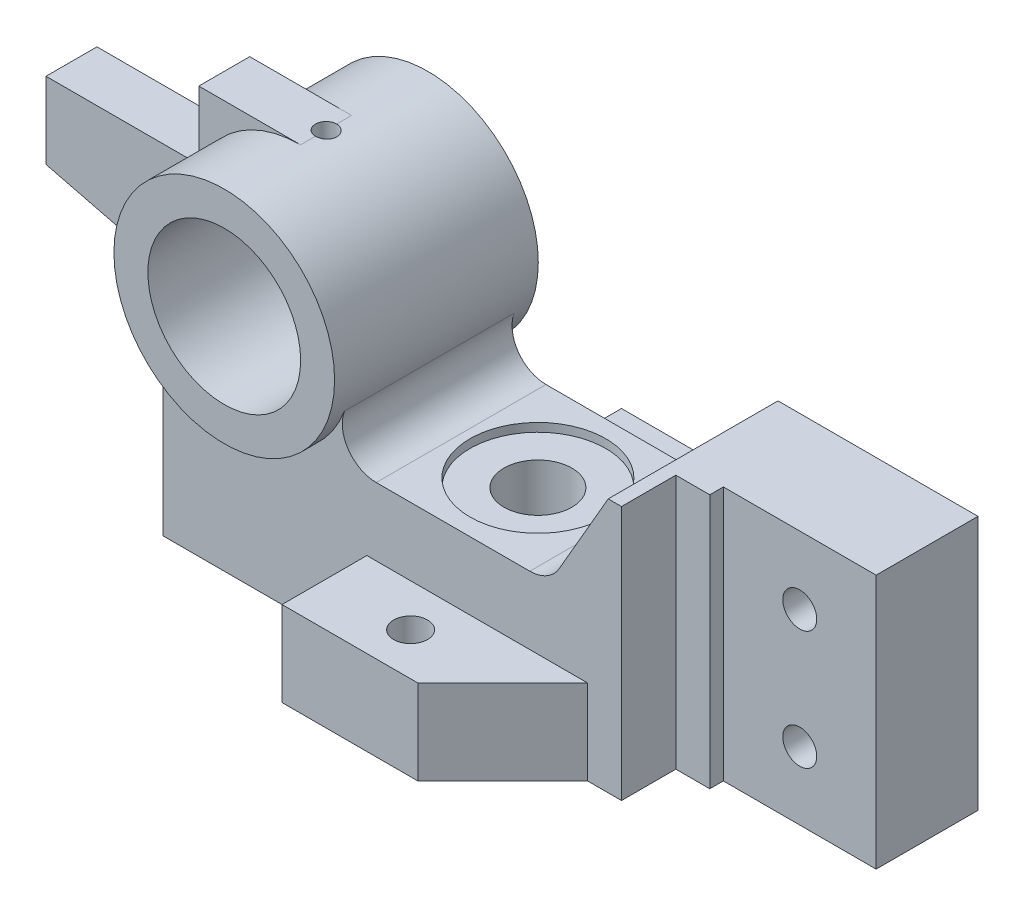
SolidWorks part; units mm, degrees
ref_plane "Front Plane" through (0, 0, 0) normal (0, 0, 1) x (1, 0, 0)
ref_plane "Top Plane" through (0, 0, 0) normal (0, 1, 0) x (1, 0, 0)
ref_plane "Right Plane" through (0, 0, 0) normal (1, 0, 0) x (0, 0, -1)
sketch "Sketch1" plane through (0, 0, 0) normal (0, 0, 1) x (1, 0, 0)
  line L0 (0, 20.6375) -> (-19.05, 20.6375)
  line L1 (-19.05, 20.6375) -> (-19.05, 7.9375)
  line L2 (-19.05, 7.9375) -> (-47.625, 7.9375)
  line L3 (-47.625, 7.9375) -> (-47.625, -6.35)
  line L4 (-47.625, -6.35) -> (-14.6024, -14.5835)
  line L5 (-14.6024, -14.5835) -> (-47.625, -14.5835) construction
  line L6 (-14.6024, -14.5835) -> (-14.6024, -44.45)
  line L7 (-14.6024, -44.45) -> (106.0476, -44.45)
  line L8 (25.2507, -15.875) -> (53.975, -15.875)
  line L9 (59.4743, -12.7) -> (68.6397, 3.175)
  line L10 (68.6397, 3.175) -> (68.6397, -44.45) construction
  line L11 (68.6397, 3.175) -> (106.0476, 3.175)
  line L12 (106.0476, 3.175) -> (106.0476, -44.45)
  line L13 (23.4976, -44.45) -> (23.4976, -28.575)
  line L14 (23.4976, -28.575) -> (64.7726, -28.575)
  line L15 (64.7726, -28.575) -> (64.7726, -44.45)
  circle A0 centre (0, 0) radius 14.2875
  circle A1 centre (0, 0) radius 20.6375
  arc A2 (19.3094, -7.2838) -> (25.2507, -15.875) centre (25.2507, -9.525) ccw
  arc A3 (53.975, -15.875) -> (59.4743, -12.7) centre (53.975, -9.525) ccw
  dimension "D1" = 41.275
  dimension "D2" = 28.575
  dimension "D3" = 12.7
  dimension "D13" = 6.35
  dimension "D4" = 12.7
  dimension "D5" = 14.2875
  dimension "D6" = 28.575
  dimension "D7" = 14
  dimension "D8" = 44.45
  dimension "D9" = 28.575
  dimension "D10" = 120.65
  dimension "D11" = 30
  dimension "D12" = 47.625
  dimension "D14" = 53.975
  dimension "D15" = 41.275
  dimension "D16" = 38.1
  dimension "D17" = 15.875
extrude "Boss-Extrude1" add sketch "Sketch1" along normal mid plane 9.525 contours A3 L8 A2 A1 L6 L7 L13 L14 L15 L12 L11 L9 | A1 A0 | A1 L2 L3 L4 | L15 L14 L13 L7 | A1 L0 L1 region at (-14.6264, 17.1702, 0) region at (14.1802, 14.1802, 0) region at (-32.5158, -1.367, 0) region at (55.8173, -23.7707, 0) region at (44.1351, -36.5125, 0)
extrude "Boss-Extrude2" add sketch "Sketch1<5>" along normal mid plane 38.1 contours A1 A0 region at (14.1802, 14.1802, 0)
sketch "Sketch1<5>" plane through (0, 0, 0) normal (0, 0, 1) x (1, 0, 0) same geometry as "Sketch1"
extrude "Boss-Extrude3" add sketch "Sketch1<6>" along normal mid plane 31.75 contours A3 L8 A2 A1 L6 L7 L13 L14 L15 L12 L11 L9 | L15 L14 L13 L7 region at (55.8173, -23.7707, 0) region at (44.1351, -36.5125, 0)
sketch "Sketch1<6>" plane through (0, 0, 0) normal (0, 0, 1) x (1, 0, 0) same geometry as "Sketch1"
extrude "Boss-Extrude4" add sketch "Sketch1<7>" along normal mid plane 63.5 contours L15 L14 L13 L7 region at (44.1351, -36.5125, 0)
sketch "Sketch1<7>" plane through (0, 0, 0) normal (0, 0, 1) x (1, 0, 0) same geometry as "Sketch1"
sketch "Sketch2" plane through (0, -15.875, 0) normal (0, 1, 0) x (1, 0, 0)
  line L0 (48.8976, -31.75) -> (64.7726, -15.875)
  line L1 (23.4976, -31.75) -> (64.7726, -31.75) construction
  line L2 (64.7726, -31.75) -> (64.7726, -15.875) construction
  line L3 (64.7726, -15.875) -> (64.7726, -31.75)
  line L4 (64.7726, -31.75) -> (48.8976, -31.75)
  line L5 (68.6397, -15.875) -> (106.0476, -15.875) construction
  line L6 (39.6129, 0) -> (106.0476, 0) construction
  line L7 (106.0476, -15.875) -> (106.0476, 15.875) construction
  line L8 (64.7726, 31.75) -> (48.8976, 31.75)
  line L9 (64.7726, 15.875) -> (64.7726, 31.75)
  line L10 (48.8976, 31.75) -> (64.7726, 15.875)
  line L12 (106.0476, -3.175) -> (77.4726, -3.175)
  line L13 (77.4726, -3.175) -> (77.4726, -5.715)
  line L14 (77.4726, -5.715) -> (71.1226, -5.715)
  line L15 (71.1226, -5.715) -> (71.1226, -15.875)
  line L16 (71.1226, -15.875) -> (106.0476, -15.875)
  line L17 (106.0476, -15.875) -> (106.0476, -3.175)
  line L18 (25.2507, -15.875) -> (53.975, -15.875) construction
  circle A0 centre (39.6129, 0) radius 12.7
  circle A1 centre (39.6129, 0) radius 6.35
  point P21 (39.6129, -15.875)
  dimension "D1" = 25.4
  dimension "D2" = 12.7
  dimension "D3" = 15.875
  dimension "D5" = 28.575
  dimension "D6" = 6.35
  dimension "D7" = 12.7
  dimension "D8" = 2.54
extrude "Cut-Extrude1" cut sketch "Sketch2" against normal through all and the other way through all contours A1 | L4 L3 L0 | L8 L10 L9 | L16 L17 L12 L13 L14 L15 region at (59.481, -15.875, 26.4583) region at (59.481, -15.875, -26.4583) region at (89.1243, -15.875, 9.7167) region at (39.6129, -15.875, 0)
extrude "Cut-Extrude4" cut sketch "Sketch2<5>" against normal blind 1.5875
sketch "Sketch2<5>" plane through (0, -15.875, 0) normal (0, 1, 0) x (1, 0, 0) same geometry as "Sketch2"
sketch "Sketch3" plane through (0, -28.575, 0) normal (0, 1, 0) x (1, 0, 0)
  line L0 (39.6129, -23.8125) -> (39.6129, 23.8125) construction
  line L2 (64.7726, 15.875) -> (23.4976, 15.875) construction
  line L3 (25.2507, -15.875) -> (53.975, -15.875) construction
  circle A0 centre (39.6129, 23.8125) radius 3.175
  circle A1 centre (39.6129, -23.8125) radius 3.175
  point P4 (39.6129, 0)
  point P9 (44.1351, 15.875)
  point P12 (39.6129, -15.875)
  dimension "D1" = 6.35
  dimension "D2" = 47.625
extrude "Cut-Extrude5" cut sketch "Sketch3" against normal through all both and the other way through all
sketch "Sketch4" plane through (0, 0, 3.175) normal (0, 0, 1) x (1, 0, 0)
  line L0 (106.0476, -44.45) -> (77.4726, -44.45) construction
  line L1 (106.0476, 3.175) -> (77.4726, 3.175) construction
  line L2 (106.0476, -44.45) -> (106.0476, 3.175) construction
  circle A0 centre (91.7601, -9.525) radius 3.175
  circle A1 centre (91.7601, -31.75) radius 3.175
  point P8 (91.7601, 3.175)
  dimension "D1" = 6.35
  dimension "D2" = 22.225
  dimension "D3" = 12.7
  dimension "D4" = 14.2875
extrude "Cut-Extrude6" cut sketch "Sketch4" against normal through all
sketch "Sketch5" plane through (0, 20.6375, 0) normal (0, 1, 0) x (1, 0, 0)
  circle A0 centre (0, 0) radius 1.9844
  dimension "D1" = 3.9688
extrude "Cut-Extrude7" cut sketch "Sketch5" against normal up to surface (6.4885 mm away) up to face at (14.2875, 0, -19.05)
